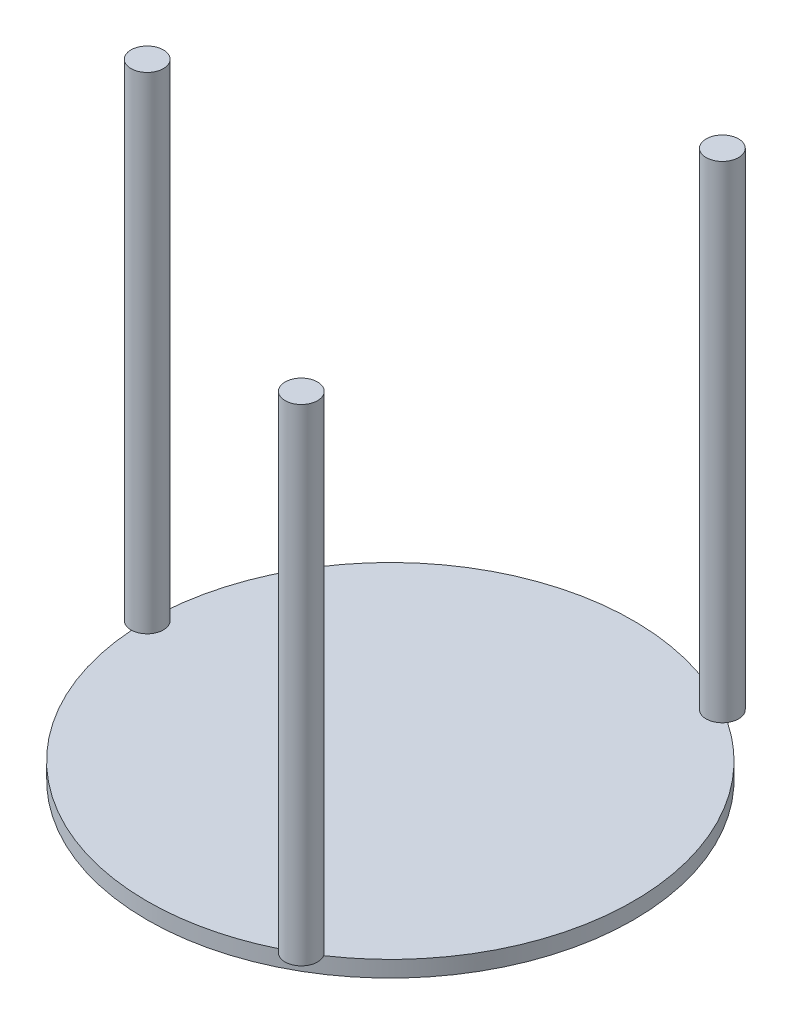
SolidWorks part; units mm, degrees
ref_plane "Front Plane" through (0, 0, 0) normal (0, 0, 1) x (1, 0, 0)
ref_plane "Top Plane" through (0, 0, 0) normal (0, 1, 0) x (1, 0, 0)
ref_plane "Right Plane" through (0, 0, 0) normal (1, 0, 0) x (0, 0, -1)
sketch "Sketch1" plane through (0, 0, 0) normal (0, 1, 0) x (1, 0, 0)
  circle A0 centre (0, 0) radius 150
  circle A1 centre (-150, 0) radius 10
  circle A2 centre (75, 129.9038) radius 10
  circle A3 centre (75, -129.9038) radius 10
  point P11 (0, 0)
  dimension "D1" = 300
  dimension "D2" = 20
  dimension "D3" = 3
extrude "Boss-Extrude1" add sketch "Sketch1" along normal blind 300 contours A1 | A2 | A3
extrude "Boss-Extrude2" add sketch "Sketch1<3>" against normal blind 10 contours A0
sketch "Sketch1<3>" plane through (0, 0, 0) normal (0, 1, 0) x (1, 0, 0) same geometry as "Sketch1"
sketch "Sketch2" plane through (0, 300, 0) normal (0, 1, 0) x (1, 0, 0)
  point P0 (-150, 0)
  point P1 (75, 129.9038)
  point P2 (75, -129.9038)
